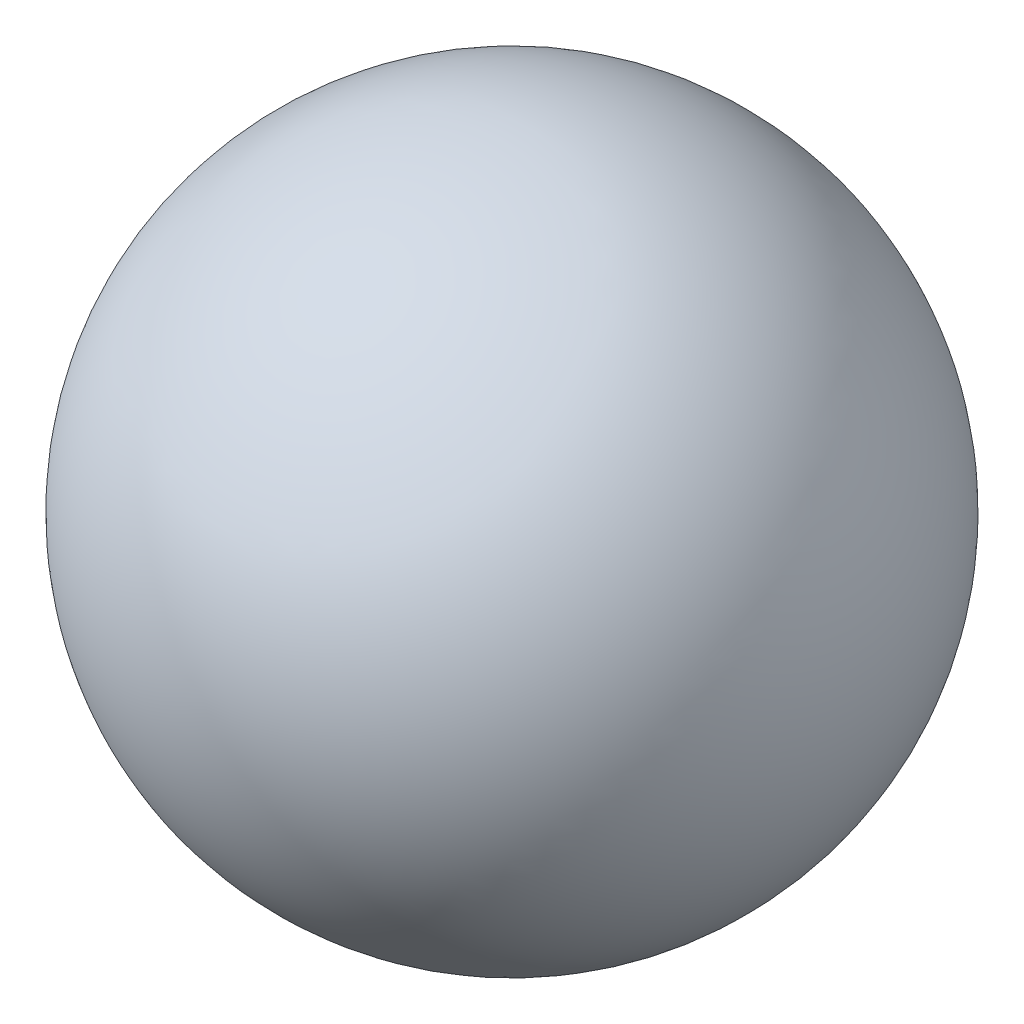
SolidWorks part; units mm, degrees
ref_plane "Front Plane" through (0, 0, 0) normal (0, 0, 1) x (1, 0, 0)
ref_plane "Top Plane" through (0, 0, 0) normal (0, 1, 0) x (1, 0, 0)
ref_plane "Right Plane" through (0, 0, 0) normal (1, 0, 0) x (0, 0, -1)
sketch "Sketch1" plane through (0, 0, 0) normal (0, 1, 0) x (1, 0, 0)
  line L0 (0, 10) -> (0, -10) construction
  line L1 (0, -10) -> (0, 10.173)
  circle A0 centre (0, 0) radius 10
  dimension "D1" = 20
revolve "Revolve4" add sketch "Sketch1" angle 360 about L0 region at (-4.2441, 0, 0)
